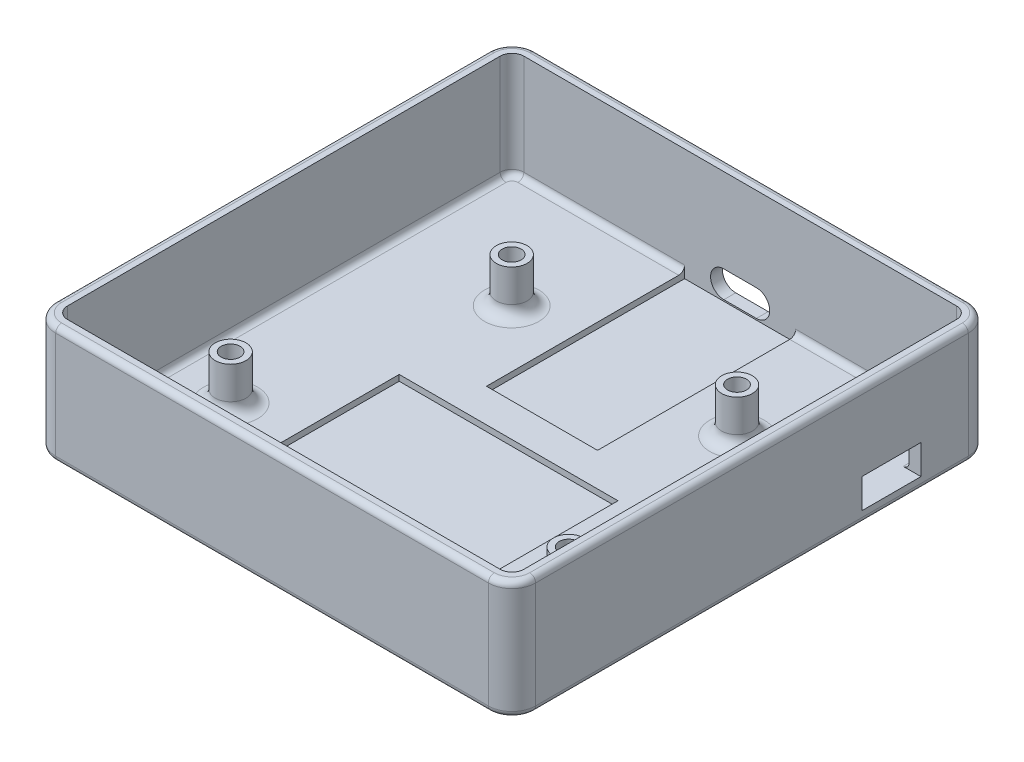
SolidWorks part; units mm, degrees
ref_plane "Front Plane" through (0, 0, 0) normal (0, 0, 1) x (1, 0, 0)
ref_plane "Top Plane" through (0, 0, 0) normal (0, 1, 0) x (1, 0, 0)
ref_plane "Right Plane" through (0, 0, 0) normal (1, 0, 0) x (0, 0, -1)
sketch "Sketch1" plane through (0, 0, 0) normal (0, 1, 0) x (1, 0, 0)
  line L1 (-38.575, -38.575) -> (38.575, -38.575)
  line L2 (-38.575, -38.575) -> (-38.575, 38.575)
  line L3 (-38.575, 38.575) -> (38.575, 38.575)
  line L4 (38.575, -38.575) -> (38.575, 38.575)
  line L5 (-38.575, -38.575) -> (38.575, 38.575) construction
  line L6 (-38.575, 38.575) -> (38.575, -38.575) construction
  point P0 (0, 0)
  dimension "D1" = 77.15
extrude "Boss-Extrude1" add sketch "Sketch1" along normal blind 2
sketch "Sketch2" plane through (0, 0, 0) normal (0, 1, 0) x (1, 0, 0)
  line L20 (38.575, -38.575) -> (38.575, 38.575) construction
  line L21 (38.575, 38.575) -> (-38.575, 38.575) construction
  line L22 (-38.575, 38.575) -> (-38.575, -38.575) construction
  line L23 (-38.575, -38.575) -> (38.575, -38.575) construction
  line L24 (40.575, -40.575) -> (40.575, 40.575)
  line L25 (40.575, 40.575) -> (-40.575, 40.575)
  line L26 (-40.575, 40.575) -> (-40.575, -40.575)
  line L27 (-40.575, -40.575) -> (40.575, -40.575)
  line L28 (40.575, -40.575) -> (40.575, 40.575)
  line L29 (40.575, 40.575) -> (-40.575, 40.575)
  line L30 (-40.575, 40.575) -> (-40.575, -40.575)
  line L31 (-40.575, -40.575) -> (40.575, -40.575)
  line L32 (38.575, -38.575) -> (38.575, 38.575)
  line L33 (38.575, 38.575) -> (-38.575, 38.575)
  line L34 (-38.575, 38.575) -> (-38.575, -38.575)
  line L35 (-38.575, -38.575) -> (38.575, -38.575)
  dimension "D1" = 2
extrude "Boss-Extrude2" add sketch "Sketch2" along normal blind 20
sketch "Sketch3" plane through (0, 2, 0) normal (0, 1, 0) x (1, 0, 0)
  line L0 (28.58, -19) -> (-28.58, -19) construction
  line L2 (19.05, 19) -> (-19.05, 19) construction
  circle A2 centre (-28.58, -19) radius 1.6
  circle A3 centre (28.58, -19) radius 1.6
  circle A4 centre (19.05, 19) radius 1.6
  circle A5 centre (-19.05, 19) radius 1.6
  circle A6 centre (-28.58, -19) radius 2.6
  circle A7 centre (-19.05, 19) radius 2.6
  circle A8 centre (28.58, -19) radius 2.6
  circle A9 centre (19.05, 19) radius 2.6
  point P0 (0, 0)
  point P2 (0, 19)
  point P17 (0, -19)
  dimension "D3" = 1
  dimension "D4" = 19
  dimension "D1" = 3.2
  dimension "D2" = 38.1
  dimension "D5" = 57.16
  dimension "D6" = 19
extrude "Boss-Extrude4" add sketch "Sketch3" along normal offset from surface (7.5 mm away) 10.5 up to face at (0, 20, 0)
sketch "Sketch4" plane through (0, 0, 0) normal (1, 0, 0) x (0, 0, -1)
  line L0 (0, 0) -> (0, 20) construction
  line L1 (-40.575, 20) -> (40.575, 20) construction
sketch "Sketch11" plane through (0, 2, 0) normal (0, 1, 0) x (1, 0, 0)
  line L0 (-17.5, -31.575) -> (-17.5, -1.575)
  line L6 (-18.5, -32.575) -> (18.5, -32.575)
  line L7 (-18.5, -32.575) -> (-18.5, -0.575)
  line L8 (-18.5, -0.575) -> (18.5, -0.575)
  line L9 (18.5, -32.575) -> (18.5, -0.575)
  line L10 (-18.5, -32.575) -> (18.5, -0.575) construction
  line L11 (-18.5, -0.575) -> (18.5, -32.575) construction
  line L12 (38.575, 38.575) -> (-38.575, 38.575) construction
  line L13 (-8.89, 38.575) -> (8.89, 38.575) construction
  line L14 (-8.89, 38.575) -> (-8.89, 5.575) construction
  line L15 (-8.89, 5.575) -> (8.89, 5.575) construction
  line L16 (8.89, 38.575) -> (8.89, 5.575) construction
  line L17 (-8.89, 38.575) -> (8.89, 5.575) construction
  line L18 (-8.89, 5.575) -> (8.89, 38.575) construction
  line L27 (-17.5, -1.575) -> (17.5, -1.575)
  line L28 (17.5, -31.575) -> (17.5, -1.575)
  line L29 (-17.5, -31.575) -> (17.5, -31.575)
  line L30 (0, -11) -> (0, 11) construction
  line L31 (4, 38.575) -> (5.5, 38.575)
  line L32 (4, 38.575) -> (4, 10.575)
  line L33 (4, 10.575) -> (5.5, 10.575)
  line L34 (5.5, 38.575) -> (5.5, 10.575)
  line L35 (-4, 10.575) -> (-5.5, 10.575)
  line L36 (-5.5, 38.575) -> (-5.5, 10.575)
  line L37 (-4, 38.575) -> (-5.5, 38.575)
  line L38 (-4, 38.575) -> (-4, 10.575)
  line L39 (-38.575, -38.575) -> (38.575, -38.575) construction
  point P1 (0, 22.075)
  point P6 (0, -16.575)
  dimension "D1" = 33
  dimension "D2" = 17.78
  dimension "D3" = 1
  dimension "D4" = 35
  dimension "D5" = 6
  dimension "D6" = 30
  dimension "D7" = 4
  dimension "D8" = 1.5
  dimension "D9" = 5
extrude "Boss-Extrude7" [suppressed] add sketch "Sketch11" along normal blind 1 contours L35 L36 L37 L38 | L32 L31 L34 L33
sketch "Sketch17" plane through (0, 2, 0) normal (0, 1, 0) x (1, 0, 0)
  line L16 (9.39, 11.075) -> (11.39, 11.075)
  line L17 (11.39, 11.075) -> (11.39, 3.075)
  line L18 (11.39, 3.075) -> (-11.39, 3.075)
  line L19 (-9.39, 5.075) -> (-9.39, 38.575)
  line L20 (9.39, 5.075) -> (-9.39, 5.075)
  line L21 (9.39, 38.575) -> (9.39, 5.075)
  line L22 (-9.39, 5.075) -> (-9.39, 11.075)
  line L23 (9.39, 5.075) -> (-9.39, 5.075)
  line L24 (9.39, 11.075) -> (9.39, 5.075)
  line L25 (-11.39, 3.075) -> (-11.39, 11.075)
  line L26 (-11.39, 11.075) -> (-9.39, 11.075)
  dimension "D1" = 0.5
  dimension "D2" = 2
  dimension "D3" = 2
  dimension "D4" = 8
extrude "Boss-Extrude8" [suppressed] add sketch "Sketch17" along normal blind 2
sketch "Sketch15" plane through (0, 2, 0) normal (0, 1, 0) x (1, 0, 0)
  line L0 (-18.5, -0.575) -> (-18.5, -8.575)
  line L1 (-18.5, -32.575) -> (-18.5, -0.575) construction
  line L2 (-18.5, -8.575) -> (-20.5, -8.575)
  line L3 (-20.5, -8.575) -> (-20.5, 1.425)
  line L4 (-20.5, 1.425) -> (-13.5, 1.425)
  line L5 (-13.5, 1.425) -> (-13.5, -0.575)
  line L6 (-18.5, -0.575) -> (18.5, -0.575) construction
  line L7 (-13.5, -0.575) -> (-18.5, -0.575)
  line L8 (-20.5, -24.575) -> (-18.5, -24.575)
  line L9 (-18.5, -24.575) -> (-18.5, -32.575)
  line L10 (-18.5, -32.575) -> (-13.5, -32.575)
  line L11 (-18.5, -32.575) -> (18.5, -32.575) construction
  line L12 (-13.5, -32.575) -> (-13.5, -34.575)
  line L13 (-13.5, -34.575) -> (-20.5, -34.575)
  line L14 (-20.5, -24.575) -> (-20.5, -34.575)
  line L15 (0, -11) -> (0, 11) construction
  line L16 (20.5, -24.575) -> (18.5, -24.575)
  line L17 (18.5, -24.575) -> (18.5, -32.575)
  line L18 (18.5, -32.575) -> (13.5, -32.575)
  line L19 (13.5, -32.575) -> (13.5, -34.575)
  line L20 (13.5, -34.575) -> (20.5, -34.575)
  line L21 (20.5, -24.575) -> (20.5, -34.575)
  line L22 (13.5, 1.425) -> (13.5, -0.575)
  line L23 (20.5, 1.425) -> (13.5, 1.425)
  line L24 (20.5, -8.575) -> (20.5, 1.425)
  line L25 (18.5, -8.575) -> (20.5, -8.575)
  line L26 (18.5, -0.575) -> (18.5, -8.575)
  line L27 (13.5, -0.575) -> (18.5, -0.575)
  dimension "D1" = 7
  dimension "D2" = 10
  dimension "D4" = 2
extrude "Boss-Extrude6" [suppressed] add sketch "Sketch15" along normal blind 1.5 contours L7 L0 L2 L3 L4 L5 | L22 L27 L26 L25 L24 L23 | L14 L13 L12 L10 L9 L8 | L16 L17 L18 L19 L20 L21
sketch "Sketch18" plane through (0, 2, 0) normal (0, 1, 0) x (1, 0, 0)
  line L0 (18.5, -32.575) -> (18.5, -0.575) construction
  line L1 (-18.5, -0.575) -> (18.5, -0.575) construction
  line L2 (-18.5, -32.575) -> (-18.5, -0.575) construction
  line L3 (-18.5, -32.575) -> (18.5, -32.575) construction
  line L4 (18.5, -32.575) -> (18.5, -0.575)
  line L5 (-18.5, -0.575) -> (18.5, -0.575)
  line L6 (-18.5, -32.575) -> (-18.5, -0.575)
  line L7 (-18.5, -32.575) -> (18.5, -32.575)
  line L21 (-8.89, 38.575) -> (8.89, 38.575) construction
  line L22 (-9.39, 38.575) -> (9.39, 38.575)
  line L24 (-9.39, 5.075) -> (-9.39, 38.575)
  line L25 (9.39, 5.075) -> (-9.39, 5.075)
  line L26 (9.39, 38.575) -> (9.39, 5.075)
  line L27 (-9.39, 5.075) -> (-9.39, 38.575)
  line L28 (9.39, 5.075) -> (-9.39, 5.075)
  line L29 (9.39, 38.575) -> (9.39, 5.075)
  dimension "D1" = 0.5
extrude "Cut-Extrude4" cut sketch "Sketch18" against normal offset from surface (1 mm away) 1 up to face at (0, 0, 0)
sketch "Sketch7" plane through (0, 0, 0) normal (0, -1, 0) x (1, 0, 0)
  line L0 (40.575, -40.575) -> (-40.575, -40.575) construction
  line L1 (-40.575, -40.575) -> (-40.575, 40.575) construction
  line L2 (0, 0) -> (-24.575, -24.575) construction
  circle A0 centre (-24.575, -24.575) radius 4
  circle A1 centre (-24.575, 24.575) radius 4
  circle A2 centre (24.575, 24.575) radius 4
  circle A3 centre (24.575, -24.575) radius 4
  dimension "D1" = 8
  dimension "D4" = 4
extrude "Cut-Extrude1" cut sketch "Sketch7" against normal offset from surface (1 mm away) 1 up to face at (28.58, 2, 16.4)
sketch "Sketch10" plane through (0, 0, -38.575) normal (0, 0, -1) x (-1, 0, 0)
  line L0 (-2.75, 3.5) -> (2.75, 3.5) construction
  line L1 (-2.75, 5.75) -> (2.75, 5.75)
  line L2 (-2.75, 1.25) -> (2.75, 1.25)
  line L3 (-38.575, 2) -> (-9.39, 2) construction
  line L4 (-38.575, 2) -> (-9.39, 2) construction
  line L5 (-9.39, 1) -> (9.39, 1) construction
  arc A1 (-2.75, 5.75) -> (-2.75, 1.25) centre (-2.75, 3.5) ccw
  arc A2 (2.75, 1.25) -> (2.75, 5.75) centre (2.75, 3.5) ccw
  point P2 (0, 3.5)
  dimension "D1" = 5.5
  dimension "D2" = 4.5
  dimension "D3" = 2.5
extrude "Cut-Extrude2" cut sketch "Sketch10" along normal up to surface (2 mm away) up to face at (0, 10, -40.575)
sketch "Sketch16" plane through (38.575, 0, 0) normal (-1, 0, 0) x (0, 0, 1)
  line L0 (38.575, 2) -> (-38.575, 2) construction
  line L1 (-28.575, 2) -> (-18.575, 2)
  line L2 (-28.575, 2) -> (-28.575, 7)
  line L3 (-28.575, 7) -> (-18.575, 7)
  line L4 (-18.575, 2) -> (-18.575, 7)
  dimension "D1" = 10
  dimension "D2" = 5
  dimension "D3" = 10
extrude "Cut-Extrude3" cut sketch "Sketch16" against normal up to surface (2 mm away) up to face at (40.575, 10, 0)
fillet "Fillet1" radius 2 4 edges at (28.58, 2, 16.4) (19.05, 2, -21.6) (-28.58, 2, 16.4) (-19.05, 2, -21.6)
fillet "Fillet2" [suppressed] radius 1
chamfer "Chamfer1" [suppressed] distance 2.5 angle 45
fillet "Fillet3" [suppressed] radius 2 tangent propagation no
fillet "Fillet6" radius 4 4 edges at (40.575, 10, -40.575) (-40.575, 10, -40.575) (-40.575, 10, 40.575) (40.575, 10, 40.575)
fillet "Fillet7" radius 2 4 edges at (38.575, 11, -38.575) (-38.575, 11, -38.575) (-38.575, 11, 38.575) (38.575, 11, 38.575)
fillet "Fillet5" radius 1 16 edges at (0, 20, 40.575) (-40.575, 20, 0) (0, 20, -40.575) (0, 0, 40.575) (-40.575, 0, 0) (0, 0, -40.575) (40.575, 20, 0) (40.575, 0, 0) (39.4034, 0, 39.4034) (-39.4034, 0, 39.4034) (-39.4034, 0, -39.4034) (39.4034, 0, -39.4034) (39.4034, 20, 39.4034) (-39.4034, 20, 39.4034) (-39.4034, 20, -39.4034) (39.4034, 20, -39.4034)
fillet "Fillet9" radius 1 10 edges at (22.9825, 2, -38.575) (37.9892, 2, -37.9892) (38.575, 2, 9) (37.9892, 2, 37.9892) (0, 2, 38.575) (-37.9892, 2, 37.9892) (-38.575, 2, 0) (-37.9892, 2, -37.9892) (38.575, 2, -32.575) (-22.9825, 2, -38.575)
